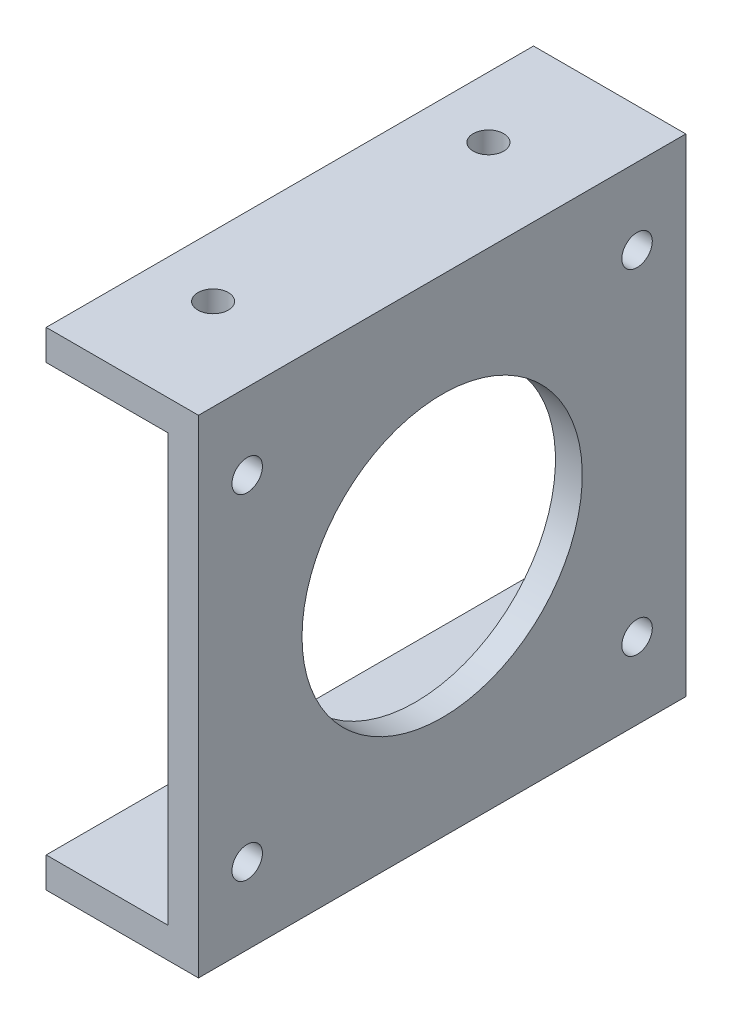
SolidWorks part; units mm, degrees
material "6061 Alloy"
ref_plane "Front Plane" through (0, 0, 0) normal (0, 0, 1) x (1, 0, 0)
ref_plane "Top Plane" through (0, 0, 0) normal (0, 1, 0) x (1, 0, 0)
ref_plane "Right Plane" through (0, 0, 0) normal (1, 0, 0) x (0, 0, -1)
sketch "Sketch1" plane through (0, 0, 0) normal (0, 0, 1) x (1, 0, 0)
  line L0 (0, 35) -> (20, 35)
  line L1 (0, -55) -> (0, 55) construction
  line L2 (20, 35) -> (20, -35)
  line L3 (20, -35) -> (0, -35)
  line L4 (0, -35) -> (0, -40)
  line L5 (0, -40) -> (25, -40)
  line L6 (25, -40) -> (25, 40)
  line L7 (25, 40) -> (0, 40)
  line L8 (0, 40) -> (0, 35)
  line L9 (55, 0) -> (-55, 0) construction
  dimension "D1" = 35
  dimension "D2" = 70
  dimension "D3" = 80
  dimension "D4" = 5
  dimension "D5" = 5
  dimension "D6" = 20
extrude "Boss-Extrude1" add sketch "Sketch1" along normal blind 80
sketch "Sketch2" plane through (20, 0, 0) normal (-1, 0, 0) x (0, 0, 1)
  line L0 (13.75, 0) -> (-13.75, 0) construction
  line L1 (0, -13.75) -> (0, 13.75) construction
  circle A0 centre (40, 0) radius 26
  dimension "D1" = 52
  dimension "D2" = 40
extrude "Cut-Extrude1" cut sketch "Sketch2" against normal blind 0.6
fillet "Fillet1" radius 0.6 1 edges at (20.6, -26, 40)
sketch "Sketch3" plane through (20.6, 0, 0) normal (-1, 0, 0) x (0, 0, 1)
  line L0 (13.75, 0) -> (-13.75, 0) construction
  circle A0 centre (40, 0) radius 23
  circle A1 centre (40, 0) radius 25.4 construction
  dimension "D1" = 46
extrude "Cut-Extrude2" cut sketch "Sketch3" against normal up to surface (4.4 mm away) up to face at (25, 0, 40)
hole_wizard "M6x1.0 Tapped Hole1" positions "Sketch6" profile "Sketch5" tap size "M6x1.0" standard "ANSI Metric" end condition through all
sketch "Sketch6" plane through (0, 40, 0) normal (0, 1, 0) x (1, 0, 0)
  line L0 (0, -44) -> (0, 44) construction
  line L1 (-13.75, 0) -> (13.75, 0) construction
  point P0 (10, -17.4)
  point P2 (10, -62.6)
  dimension "D1" = 10
  dimension "D2" = 45.2
  dimension "D3" = 17.4
sketch "Sketch5" plane through (10, 40, 17.4) normal (1, 0, 0) x (0, 0, 1)
  line L0 (0, 0) -> (0, 80)
  line L1 (0, 80) -> (2.5, 80)
  line L2 (2.5, 80) -> (2.5, 0)
  line L5 (2.5, 0) -> (0, 0)
  line L11 (0, -6.35) -> (0, 107.95) construction
  dimension "Thread Major Dia." = 5
  dimension "Thru Tap Drill Depth" = 80
hole_wizard "M6x1.0 Tapped Hole2" positions "Sketch7" profile "Sketch8" tap size "M6x1.0" standard "ANSI Metric" end condition through all
sketch "Sketch7" plane through (25, 0, 0) normal (1, 0, 0) x (0, 0, -1)
  line L0 (-80, -40) -> (-80, 40) construction
  line L1 (0, 13.75) -> (0, -13.75) construction
  line L2 (-80, 40) -> (0, 40) construction
  line L3 (-80, -40) -> (0, -40) construction
  point P0 (-72, 27.5)
  point P2 (-8, 27.5)
  point P4 (-8, -27.5)
  point P6 (-72, -27.5)
  point P9 (0, 0)
  point P10 (0, 0)
  point P11 (0, 0)
  point P12 (0, 0)
  dimension "D1" = 8
  dimension "D2" = 8
  dimension "D3" = 12.5
  dimension "D4" = 12.5
sketch "Sketch8" plane through (25, 27.5, 72) normal (0, 1, 0) x (0, 0, -1)
  line L0 (0, 0) -> (0, 25)
  line L1 (0, 25) -> (2.5, 25)
  line L2 (2.5, 25) -> (2.5, 0)
  line L5 (2.5, 0) -> (0, 0)
  line L11 (0, -6.35) -> (0, 107.95) construction
  dimension "Thread Major Dia." = 5
  dimension "Thru Tap Drill Depth" = 25
